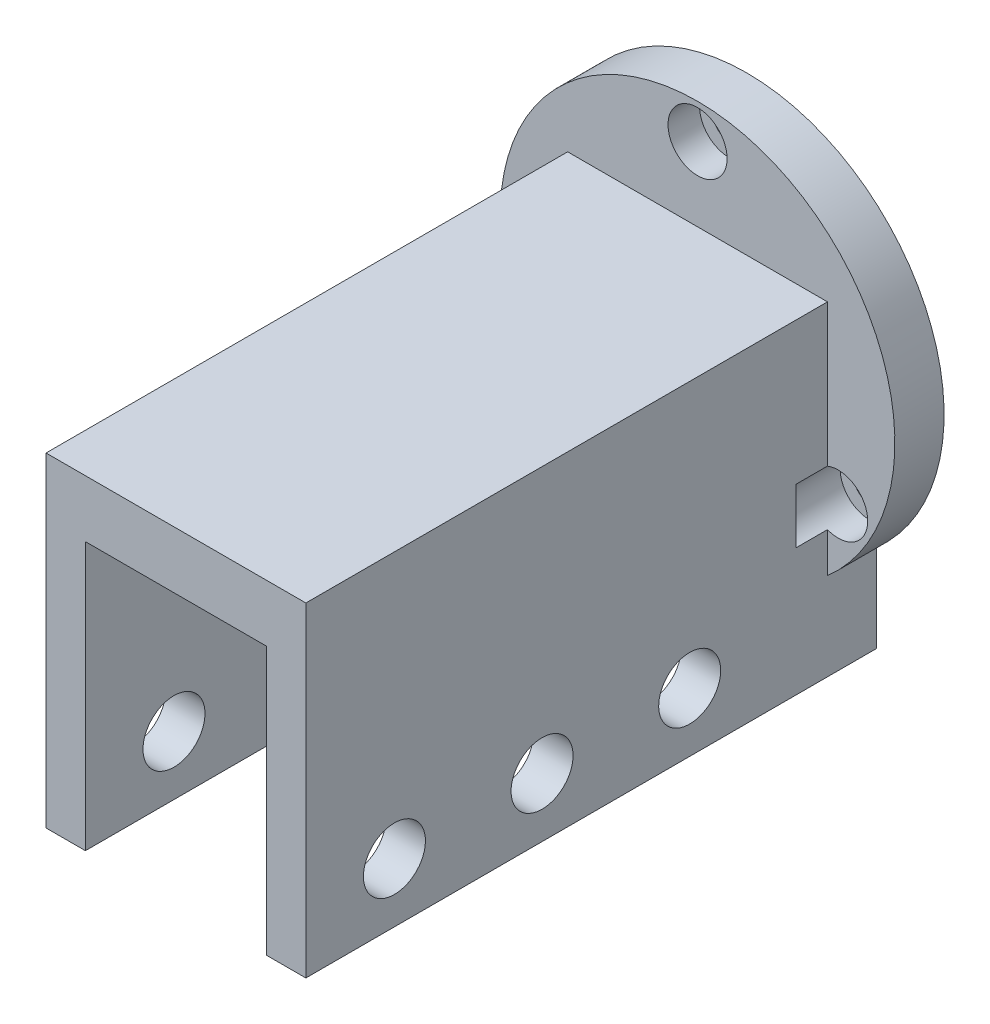
SolidWorks part; units mm, degrees
ref_plane "前基準面" through (0, 0, 0) normal (0, 0, 1) x (1, 0, 0)
ref_plane "上基準面" through (0, 0, 0) normal (0, 1, 0) x (1, 0, 0)
ref_plane "右基準面" through (0, 0, 0) normal (1, 0, 0) x (0, 0, -1)
sketch "草圖1" plane through (0, 0, 0) normal (0, 0, 1) x (1, 0, 0)
  line L0 (0, 0) -> (0, 33)
  line L5 (0, 33) -> (26.4, 33)
  line L6 (26.4, 33) -> (26.4, 0)
  line L12 (26.4, 0) -> (22.4, 0)
  line L13 (22.4, 0) -> (22.4, 27.2)
  line L14 (22.4, 27.2) -> (4, 27.2)
  line L15 (4, 27.2) -> (4, 0)
  line L16 (4, 0) -> (0, 0)
  dimension "D1" = 27.2
  dimension "D2" = 33
  dimension "D3" = 4
  dimension "D4" = 4
  dimension "D5" = 26.4
extrude "填料-伸長1" add sketch "草圖1" along normal mid plane 48
sketch "草圖3" plane through (26.4, 0, 0) normal (1, 0, 0) x (0, 0, -1)
  line L0 (-24, 0) -> (24, 0) construction
  line L1 (0, 0) -> (0, 16.3853) construction
  circle A0 centre (0, 6) radius 3.15
  circle A1 centre (15, 6) radius 3.15
  circle A2 centre (-15, 6) radius 3.15
  dimension "D1" = 6.3
  dimension "D2" = 6
  dimension "D3" = 15
extrude "除料-伸長2" cut sketch "草圖3" against normal up to surface (26.4 mm away) up to face at (0, 16.5, 0)
sketch "草圖4" plane through (0, 0, -24) normal (0, 0, -1) x (-1, 0, 0)
  line L0 (-4, 0) -> (-4, 27.2) construction
  line L1 (-26.4, 33) -> (0, 33)
  line L2 (-26.4, 33) -> (-26.4, 0)
  line L3 (-26.4, 0) -> (0, 0)
  line L4 (0, 33) -> (0, 0)
  line L5 (-22.4, 27.2) -> (-4, 27.2)
  line L6 (-22.4, 27.2) -> (-22.4, 10)
  line L7 (-22.4, 10) -> (-4, 10)
  line L8 (-4, 27.2) -> (-4, 10)
  line M9 (-4, 0) -> (0, 0)
  line M10 (0, 0) -> (0, 33)
  line M11 (0, 33) -> (-26.4, 33)
  line M12 (-26.4, 33) -> (-26.4, 0)
  line M13 (-26.4, 0) -> (-22.4, 0)
  line M14 (-22.4, 0) -> (-22.4, 27.2)
  line M15 (-22.4, 27.2) -> (-4, 27.2)
  line M16 (-4, 27.2) -> (-4, 0)
  dimension "D1" = 10
extrude "填料-伸長2" add sketch "草圖4" along normal blind 10 contours M16 M9 M10 M11 M12 M13 M14 M15 | L7 M14 M16 M15 | L7 L3 M14 M16 region at (13.2, 32.5774, -24) region at (13.2, 5, -24) region at (13.2, 18.6, -24)
extrude "除料-伸長4" cut sketch "草圖4<3>" along normal blind 5 contours L7 M14 M16 M15 region at (13.2, 18.6, -24)
sketch "草圖4<3>" plane through (0, 0, -24) normal (0, 0, -1) x (-1, 0, 0) same geometry as "草圖4"
extrude "除料-伸長6" cut sketch "草圖4<5>" along normal blind 2 contours L7 L3 M14 M16 region at (13.2, 5, -24)
sketch "草圖4<5>" plane through (0, 0, -24) normal (0, 0, -1) x (-1, 0, 0) same geometry as "草圖4"
sketch "草圖2" plane through (60.4, 53.6, -34) normal (0, 0, 1) x (0, -1, 0)
  line L0 (20.6, -47.2) -> (35.8595, -47.2) construction
  line L1 (20.6, -60.4) -> (20.6, -34) construction
  circle A0 centre (29.6, -47.2) radius 20.05
  circle A1 centre (13.1, -47.2) radius 1.6
  circle A2 centre (37.85, -32.9106) radius 1.6
  circle A3 centre (37.85, -61.4894) radius 1.6
  point P11 (13.1, -47.2)
  point P13 (29.6, -47.2)
  dimension "D1" = 40.1
  dimension "D2" = 3.2
  dimension "D5" = 9
  dimension "D3" = 16.5
  dimension "D4" = 3
extrude "填料-伸長3" add sketch "草圖2" along normal blind 5
sketch "草圖7" plane through (0, 0, -29) normal (0, 0, 1) x (1, 0, 0)
  circle A0 centre (27.4894, 15.75) radius 1.6
  circle A1 centre (-1.0894, 15.75) radius 1.6
extrude "除料-伸長7" cut sketch "草圖7" against normal through all
sketch "草圖8" plane through (0, 0, -29) normal (0, 0, 1) x (1, 0, 0)
  circle A0 centre (-1.0894, 15.75) radius 3
  circle A1 centre (27.4894, 15.75) radius 3
  circle A2 centre (13.2, 40.5) radius 3
  dimension "D1" = 6
  dimension "D2" = 6
  dimension "D3" = 6
extrude "除料-伸長8" cut sketch "草圖8" against normal blind 3.2 and the other way blind 3.2
